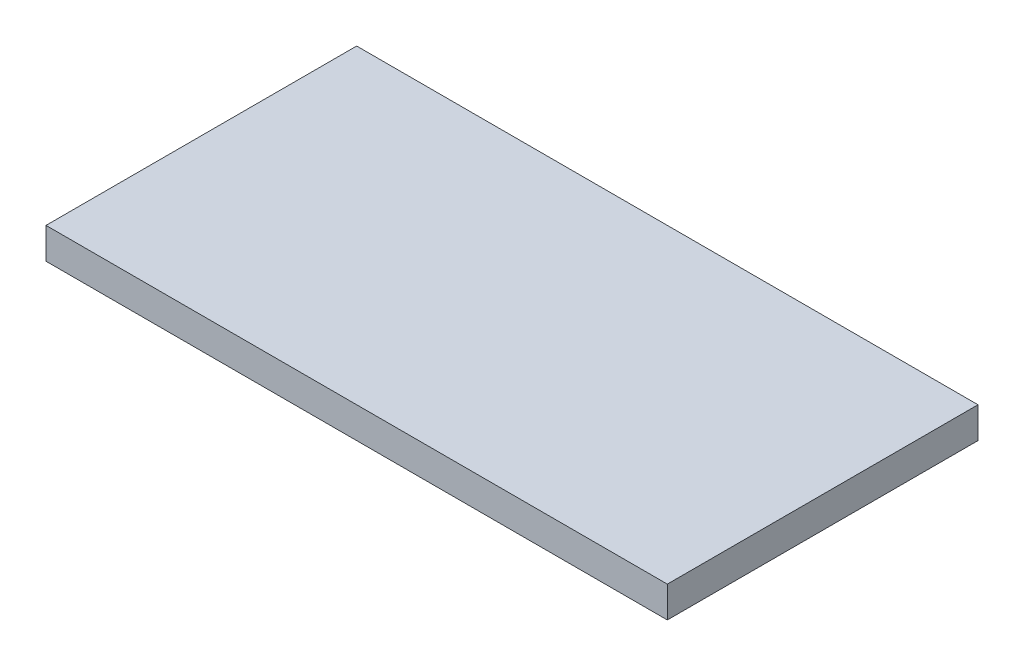
SolidWorks part; units mm, degrees
ref_plane "Front Plane" through (0, 0, 0) normal (0, 0, 1) x (1, 0, 0)
ref_plane "Top Plane" through (0, 0, 0) normal (0, 1, 0) x (1, 0, 0)
ref_plane "Right Plane" through (0, 0, 0) normal (1, 0, 0) x (0, 0, -1)
sketch "Sketch1" plane through (0, 0, 0) normal (0, 1, 0) x (1, 0, 0)
  line L0 (0, -10) -> (0, 10) construction
  line L1 (-10, -10) -> (10, -10)
  line L2 (-10, -10) -> (-10, 10)
  line L3 (-10, 10) -> (10, 10)
  line L4 (10, -10) -> (10, 10)
  line L5 (-10, -10) -> (10, 10) construction
  line L6 (-10, 10) -> (10, -10) construction
  line L7 (-10, -10) -> (-20, -10)
  line L8 (-10, -10) -> (-10, 10)
  line L9 (-10, 10) -> (-20, 10)
  line L10 (-20, -10) -> (-20, 10)
  line L11 (10, -10) -> (20, -10)
  line L12 (20, -10) -> (20, 10)
  line L13 (10, 10) -> (20, 10)
  line L14 (-20, 10) -> (20, -10) construction
  line L15 (20, 10) -> (-20, -10) construction
  point P0 (0, 0)
  dimension "D1" = 20
  dimension "D2" = 20
  dimension "D3" = 10
extrude "Boss-Extrude1" add sketch "Sketch1" against normal blind 2 contours L10 L7 L2 L9 | L1 L4 L3 L2 | L13 L4 L11 L12 region at (0, 0, 0) region at (-15, 0, 0) region at (15, 0, 0)
